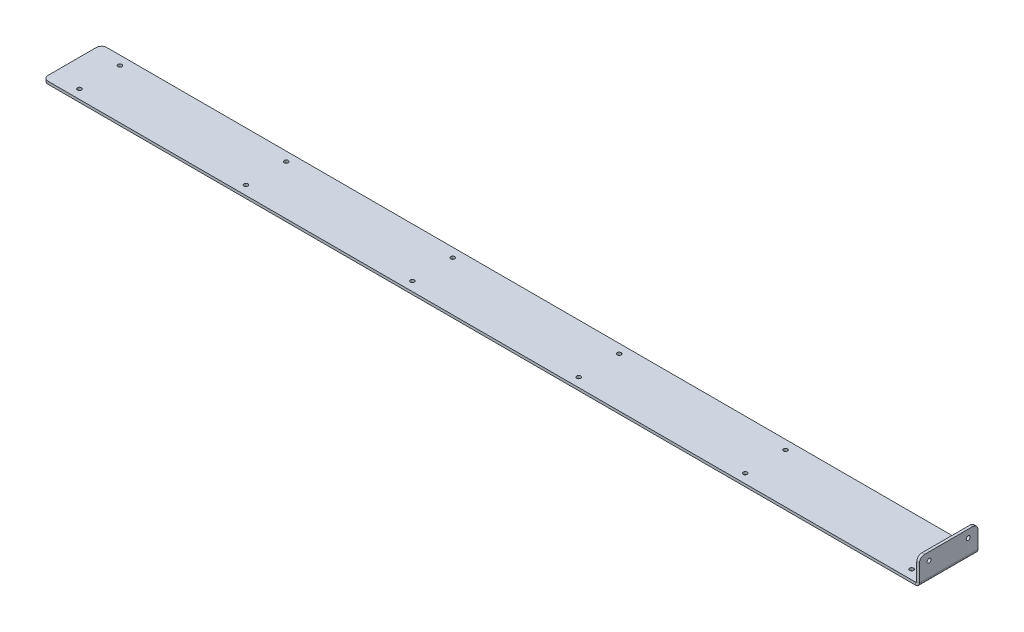
SolidWorks part; units mm, degrees
note: The reader was unsure of these and kept them because the rebuilt part matched: flange length of "Edge-Flange2".
material "5052-H32"
ref_plane "Front Plane" through (0, 0, 0) normal (0, 0, 1) x (1, 0, 0)
ref_plane "Top Plane" through (0, 0, 0) normal (0, 1, 0) x (1, 0, 0)
ref_plane "Right Plane" through (0, 0, 0) normal (1, 0, 0) x (0, 0, -1)
sketch "Sketch1" plane through (0, 0, 0) normal (0, 1, 0) x (1, 0, 0)
  line L1 (-1063.9234, 35.7187) -> (0, 35.7188)
  line L2 (-1063.9234, 35.7187) -> (-1063.9234, -35.7188)
  line L3 (-1063.9234, -35.7188) -> (0, -35.7188)
  line L4 (0, 35.7188) -> (0, -35.7188)
  point P4 (0, 0)
  dimension "D1" = 1063.9234
  dimension "D2" = 71.4375
base flange "Base-Flange1" sketch "Sketch1" thickness 3.2639 reverse thickness direction no parameters "D1"=1.27
edge flange "Edge-Flange2" sketch "Sketch11" flange angle 90 flange length 31.75 flange position bend outside bend radius 1.27 thickness 3.2639 relief rectangular parameters "D6"=10
sketch "Sketch11" plane through (0, 0, 0) normal (1, 0, 0) x (0, 0, -1)
  line L2 (-35.7188, 0) -> (-35.7188, 28.4861)
  line L3 (-35.7188, 28.4861) -> (35.7187, 28.4861)
  line L4 (35.7187, 28.4861) -> (35.7188, 0)
  line L7 (-35.7188, 0) -> (35.7188, 0) construction
  line L8 (-35.7188, 0) -> (35.7188, 0)
bend "EdgeBend2" bend radius 1.27 bend angle 90 parameters "D5"=2
sketch "Sketch12" plane through (0, 0, 0) normal (0, 1, 0) x (1, 0, 0)
  line L0 (4.5339, 35.7187) -> (4.5339, -35.7188) construction
  line L1 (-16.1036, 24.6062) -> (-16.1036, -24.6062) construction
  point P0 (-16.1036, 24.6062)
  point P1 (-16.1036, -24.6062)
  point P7 (-16.1036, 0)
  dimension "D1" = 24.6062
  dimension "D2" = 20.6375
hole_wizard "#10 (0.1935) Diameter Hole1" positions "Sketch13" profile "Sketch14" hole size "#10" standard "ANSI Inch" end condition up to next
sketch "Sketch13" plane through (0, 0, 0) normal (0, 1, 0) x (1, 0, 0)
  point P0 (-16.1036, 24.6062)
  point P3 (-16.1036, -24.6062)
sketch "Sketch14" plane through (-16.1036, 0, -24.6062) normal (1, 0, 0) x (0, 0, 1)
  line L0 (0, 0) -> (0, 3.2639)
  line L1 (0, 3.2639) -> (2.4574, 3.2639)
  line L2 (2.4574, 3.2639) -> (2.4574, 0)
  line L5 (2.4574, 0) -> (0, 0)
  line L11 (0, -6.35) -> (0, 107.95) construction
  dimension "Thru Hole Dia." = 4.9149
  dimension "Thru Hole Depth" = 3.2639
pattern_linear "LPattern1" count 6 spacing 202.8825 along (-1, 0, 0) of "#10 (0.1935) Diameter Hole1"
sketch "Sketch15" plane through (1.27, 0, 0) normal (-1, 0, 0) x (0, 0, 1)
  line L0 (23.8125, 19.05) -> (-23.8125, 19.05)
  line L1 (35.7188, 0) -> (-35.7188, 0) construction
  point P3 (0, 19.05)
  dimension "D1" = 19.05
  dimension "D2" = 47.625
hole_wizard "#10 (0.1935) Diameter Hole2" positions "Sketch17" profile "Sketch18" hole size "#10" standard "ANSI Inch" end condition up to next
sketch "Sketch17" plane through (1.27, 0, 0) normal (-1, 0, 0) x (0, 0, 1)
  point P0 (-23.8125, 19.05)
  point P3 (23.8125, 19.05)
sketch "Sketch18" plane through (1.27, 19.05, -23.8125) normal (0, 1, 0) x (0, 0, 1)
  line L0 (0, 0) -> (0, 3.2639)
  line L1 (0, 3.2639) -> (2.4574, 3.2639)
  line L2 (2.4574, 3.2639) -> (2.4574, 0)
  line L5 (2.4574, 0) -> (0, 0)
  line L11 (0, -6.35) -> (0, 107.95) construction
  dimension "Thru Hole Dia." = 4.9149
  dimension "Thru Hole Depth" = 3.2639
fillet "Fillet1" radius 6.35 4 edges at (-1063.9234, -1.632, 35.7188) (-1063.9234, -1.632, -35.7187) (2.902, 28.4861, -35.7187) (2.902, 28.4861, 35.7188)
sketch "Bend-Lines1" [suppressed] plane through (0, 0, 0) normal (0, 1, 0) x (1, 0, 0)
sketch "Bounding-Box1" [suppressed] plane through (0, 0, 0) normal (0, 1, 0) x (1, 0, 0)
sheet metal parameters "Sheet-Metal1" thickness 3.2639 parameters "D1"=1.27
flat pattern "Flat-Pattern1" [suppressed]
sketch "Bend-Lines2" plane through (0, 0, 0) normal (0, 1, 0) x (1, 0, 0)
sketch3d "Bounding-Box2" [suppressed]
  line L0 (0, -41.3639, 0) -> (1066.8, -41.3639, 0) construction
  line L1 (0, 41.3639, 0) -> (1066.8, 41.3639, 0) construction
  line L2 (0, -41.3639, 0) -> (0, 41.3639, 0) construction
  line L3 (1066.8, -41.3639, 0) -> (1066.8, 41.3639, 0) construction
sheet metal parameters "Sheet-Metal3" thickness 3.2639 parameters "D1"=1.27
flat pattern "Flat-Pattern1"
sketch "Bend-Lines2" plane through (0, 0, 0) normal (0, 1, 0) x (1, 0, 0)
  line L2 (2.2792, -38.1) -> (2.2792, 38.1) construction
  line L3 (2.2792, -38.1) -> (2.2792, 38.1) construction
sketch3d "Bounding-Box2" [suppressed]
  line L0 (50.8245, -38.1, 0) -> (-1055.9161, -38.1, 0) construction
  line L1 (50.8245, 38.1, 0) -> (-1055.9161, 38.1, 0) construction
  line L2 (50.8245, -38.1, 0) -> (50.8245, 38.1, 0) construction
  line L3 (-1055.9161, -38.1, 0) -> (-1055.9161, 38.1, 0) construction
bend of the flat pattern "Flatten-<EdgeBend2>1"
sheet metal parameters "Sheet-Metal4" thickness 3.2639 parameters "D1"=1.27
flat pattern "Flat-Pattern1"
sketch "Bend-Lines2" plane through (0, 0, 0) normal (0, 1, 0) x (1, 0, 0)
  line L2 (2.2792, -38.1) -> (2.2792, 38.1) construction
  line L3 (2.2792, -38.1) -> (2.2792, 38.1) construction
sketch3d "Bounding-Box2" [suppressed]
  line L0 (50.8245, -38.1, 0) -> (-1055.9161, -38.1, 0) construction
  line L1 (50.8245, 38.1, 0) -> (-1055.9161, 38.1, 0) construction
  line L2 (50.8245, -38.1, 0) -> (50.8245, 38.1, 0) construction
  line L3 (-1055.9161, -38.1, 0) -> (-1055.9161, 38.1, 0) construction
bend of the flat pattern "Flatten-<EdgeBend2>1"
sheet metal parameters "Sheet-Metal5" thickness 3.2639 parameters "D1"=1.27
flat pattern "Flat-Pattern1" [suppressed]
sketch "Bend-Lines2" plane through (0, 0, 0) normal (0, 1, 0) x (1, 0, 0)
  line L2 (2.2792, -38.1) -> (2.2792, 38.1) construction
  line L3 (2.2792, -38.1) -> (2.2792, 38.1) construction
sketch3d "Bounding-Box2" [suppressed]
  line L0 (50.8245, -38.1, 0) -> (-1049.3375, -38.1, 0) construction
  line L1 (50.8245, 38.1, 0) -> (-1049.3375, 38.1, 0) construction
  line L2 (50.8245, -38.1, 0) -> (50.8245, 38.1, 0) construction
  line L3 (-1049.3375, -38.1, 0) -> (-1049.3375, 38.1, 0) construction
bend of the flat pattern "Flatten-<EdgeBend2>1"
sketch "Sketch15-1" [suppressed] plane through (3.2884, 0, 0) normal (0, 1, 0) x (0, 0, 1)
  line L0 (25.4, 19.05) -> (-25.4, 19.05)
  line L1 (38.1, 0) -> (-38.1, 0)
  point P3 (0, 19.05)
  dimension "D1" = 19.05
  dimension "D2" = 50.8
sheet metal parameters "Sheet-Metal6" thickness 3.2639 parameters "D1"=1.27
flat pattern "Flat-Pattern1" [suppressed]
sketch "Bend-Lines2" plane through (0, 0, 0) normal (0, 1, 0) x (1, 0, 0)
  line L2 (2.2792, -35.7187) -> (2.2792, 35.7187) construction
  line L3 (2.2792, -35.7187) -> (2.2792, 35.7187) construction
sketch3d "Bounding-Box2" [suppressed]
  line L0 (-1063.9235, -35.7186, 0) -> (31.7745, -35.7188, 0) construction
  line L1 (-1063.9234, 35.7188, 0) -> (31.7745, 35.7186, 0) construction
  line L2 (-1063.9235, -35.7186, 0) -> (-1063.9234, 35.7188, 0) construction
  line L3 (31.7745, -35.7188, 0) -> (31.7745, 35.7186, 0) construction
bend of the flat pattern "Flatten-<EdgeBend2>1"
sketch "Sketch15-1" [suppressed] plane through (3.2884, 0, 0) normal (0, 1, 0) x (0, 0, 1)
  line L0 (23.8125, 19.05) -> (-23.8125, 19.05)
  line L1 (35.7188, 0) -> (-35.7188, 0) construction
  point P3 (0, 19.05)
  dimension "D1" = 19.05
  dimension "D2" = 47.625
